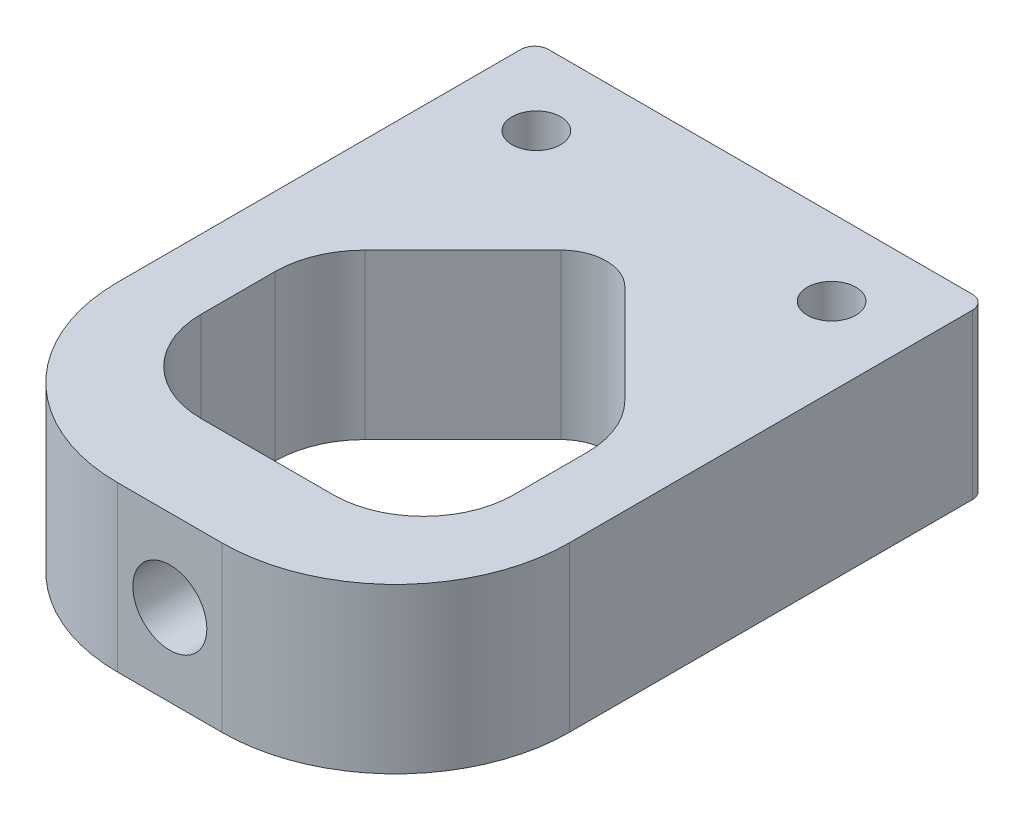
SolidWorks part; units mm, degrees
material "Delrin 2700 NC010, Low Viscosity Acetal Copolymer (SS)"
ref_plane "Front Plane" through (0, 0, 0) normal (0, 0, 1) x (1, 0, 0)
ref_plane "Top Plane" through (0, 0, 0) normal (0, 1, 0) x (1, 0, 0)
ref_plane "Right Plane" through (0, 0, 0) normal (1, 0, 0) x (0, 0, -1)
sketch "Sketch1" plane through (0, 0, 0) normal (0, 1, 0) x (1, 0, 0)
  line L1 (-27.0046, 23.0125) -> (-10.4946, 23.0125)
  line L2 (-27.0046, 23.0125) -> (-27.0046, 1.4225)
  line L3 (-27.0046, 1.4225) -> (-10.4946, 1.4225)
  line L4 (-10.4946, 23.0125) -> (-10.4946, 1.4225)
  dimension "D1" = 16.51
  dimension "D2" = 21.59
extrude "Boss-Extrude1" add sketch "Sketch1" along normal blind 6
sketch "Sketch2" plane through (0, 6, 0) normal (0, 1, 0) x (1, 0, 0)
  line L0 (-10.4946, 23.0125) -> (-27.0046, 23.0125) construction
  line L2 (-10.4946, 1.4225) -> (-10.4946, 23.0125) construction
  circle A0 centre (-24.1471, 20.2185) radius 0.7572
  circle A1 centre (-13.3521, 20.2185) radius 0.7572
  dimension "D1" = 10.795
  dimension "D2" = 2.794
  dimension "D4" = 2.8575
hole_wizard "#2-56 Tapped Hole1" positions "Sketch4" profile "Sketch3" tap size "#2-56" standard "ANSI Inch" end condition through all
sketch "Sketch4" plane through (0, 6, 0) normal (0, 1, 0) x (1, 0, 0)
  point P0 (-24.1471, 20.2185)
  point P3 (-13.3521, 20.2185)
sketch "Sketch3" plane through (-24.1471, 6, -20.2185) normal (1, 0, 0) x (0, 0, 1)
  line L0 (0, 0) -> (0, 6)
  line L1 (0, 6) -> (0.889, 6)
  line L2 (0.889, 6) -> (0.889, 0)
  line L5 (0.889, 0) -> (0, 0)
  line L11 (0, -6.35) -> (0, 107.95) construction
  dimension "Thru Tap Drill Dia." = 1.778
  dimension "Thru Tap Drill Depth" = 6
cosmetic thread "Hole Thread1"
cosmetic thread "Hole Thread2"
sketch "Sketch5" plane through (0, 6, 0) normal (0, 1, 0) x (1, 0, 0)
  line L0 (-18.7496, 23.0125) -> (-18.7496, -5.13) construction
  line L1 (-10.4946, 23.0125) -> (-27.0046, 23.0125) construction
  line L2 (-18.7496, 18.0595) -> (-13.0346, 12.3445)
  line L4 (-24.4646, 12.3445) -> (-18.7496, 18.0595)
  line L5 (-24.4646, 4.9785) -> (-13.0346, 4.9785)
  line L6 (-24.4646, 4.9785) -> (-24.4646, 12.3445)
  line L7 (-18.7496, 4.9785) -> (-18.7496, 1.4225) construction
  line L8 (-27.0046, 23.0125) -> (-27.0046, 1.4225) construction
  line L10 (-13.0346, 4.9785) -> (-13.0346, 12.3445)
  line L13 (-27.0046, 18.0595) -> (-11.7646, 18.0595) construction
  line L14 (-27.0046, 1.4225) -> (-10.4946, 1.4225) construction
  circle A0 centre (-18.7496, 10.4395) radius 5.461 construction
  circle A1 centre (-18.7496, 11.0745) radius 4.7625 construction
  circle A2 centre (-18.7496, 16.1545) radius 1.651 construction
  dimension "D1" = 11.938
  dimension "D2" = 10.922
  dimension "D3" = 9.525
  dimension "D4" = 8.255
  dimension "D8" = 4.953
  dimension "D10" = 45
  dimension "D9" = 21.59
  dimension "D12" = 11.43
  dimension "D5" = 6.858
  dimension "D6" = 12.573
  dimension "D7" = 3.556
  dimension "D11" = 45
  dimension "D13" = 5.715
  dimension "D14" = 18.034
extrude "Cut-Extrude3" cut sketch "Sketch5" against normal through all
fillet "Fillet3" radius 0.508 2 edges at (-27.0046, 3, -23.0125) (-10.4946, 3, -23.0125)
fillet "Fillet1" radius 6.35 2 edges at (-27.0046, 3, -1.4225) (-10.4946, 3, -1.4225)
fillet "Fillet4" radius 3.302 4 edges at (-13.0346, 3, -4.9785) (-24.4646, 3, -4.9785) (-13.0346, 3, -12.3445) (-24.4646, 3, -12.3445)
fillet "Fillet5" radius 1.651 1 edges at (-18.7496, 3, -18.0595)
sketch "Sketch7" plane through (0, 0, -1.4225) normal (0, 0, 1) x (1, 0, 0)
  line L0 (-18.7496, 6) -> (-18.7496, 0) construction
  line L1 (-20.6546, 6) -> (-16.8446, 6) construction
  line L2 (-20.6546, 0) -> (-16.8446, 0) construction
  line L3 (-20.6546, 3) -> (-16.8446, 3) construction
  line L4 (-20.6546, 6) -> (-20.6546, 0) construction
  line L5 (-16.8446, 0) -> (-16.8446, 6) construction
  point P12 (-18.7496, 3)
hole_wizard "#6-32 Tapped Hole1" positions "Sketch11" profile "Sketch10" tap size "#6-32" standard "ANSI Inch" end condition up to next
sketch "Sketch11" plane through (0, 0, -1.4225) normal (0, 0, 1) x (1, 0, 0)
  point P0 (-18.7496, 3)
sketch "Sketch10" plane through (-18.7496, 3, -1.4225) normal (1, 0, 0) x (0, -1, 0)
  line L0 (0, 0) -> (0, 3.556)
  line L1 (0, 3.556) -> (1.3525, 3.556)
  line L2 (1.3525, 3.556) -> (1.3525, 0)
  line L5 (1.3525, 0) -> (0, 0)
  line L11 (0, -6.35) -> (0, 107.95) construction
  dimension "Thru Tap Drill Dia." = 2.7051
  dimension "Thru Tap Drill Depth" = 3.556
cosmetic thread "Hole Thread6"
